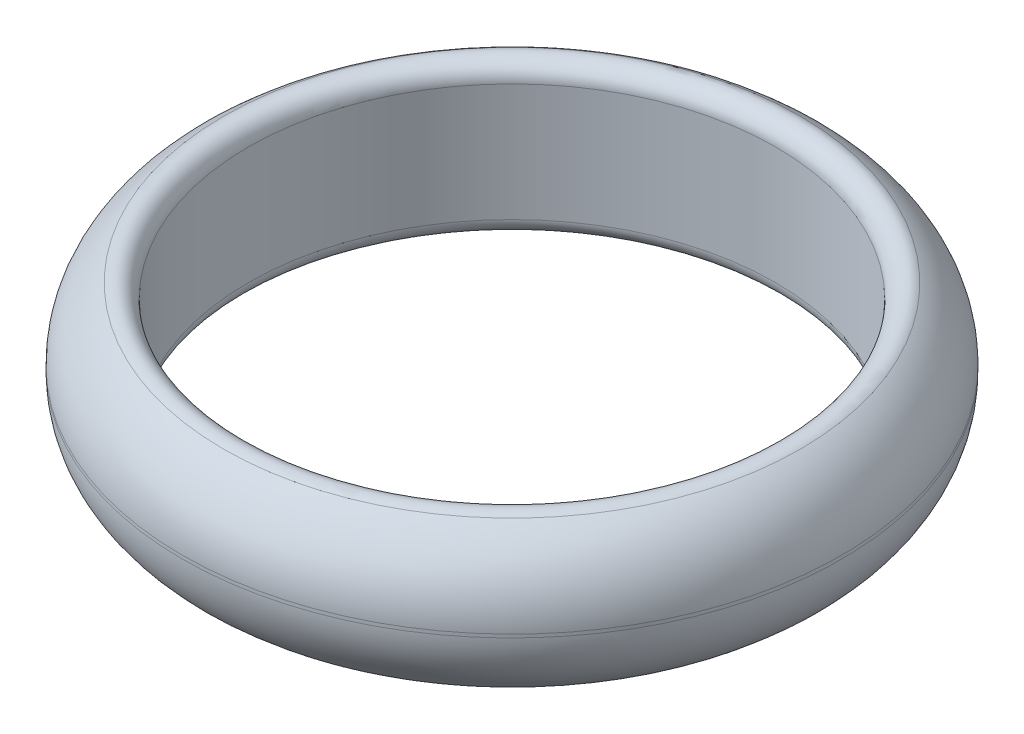
SolidWorks part; units mm, degrees
ref_plane "Front Plane" through (0, 0, 0) normal (0, 0, 1) x (1, 0, 0)
ref_plane "Top Plane" through (0, 0, 0) normal (0, 1, 0) x (1, 0, 0)
ref_plane "Right Plane" through (0, 0, 0) normal (1, 0, 0) x (0, 0, -1)
sketch "Sketch3" plane through (0, 0, 0) normal (0, 1, 0) x (1, 0, 0)
  circle A0 centre (0, 0) radius 10
extrude "Boss-Extrude1" add sketch "Sketch3" along normal blind 5
sketch "Sketch4" plane through (0, 5, 0) normal (0, 1, 0) x (1, 0, 0)
  circle A0 centre (0, 0) radius 8
extrude "Cut-Extrude1" cut sketch "Sketch4" against normal blind 5
fillet "Fillet2" radius 2.5 2 edges at (0, 0, 10) (0, 5, 10)
fillet "Fillet5" radius 0.5 1 edges at (0, 5, 8)
fillet "Fillet6" radius 0.5 1 edges at (0, 0, 8)
